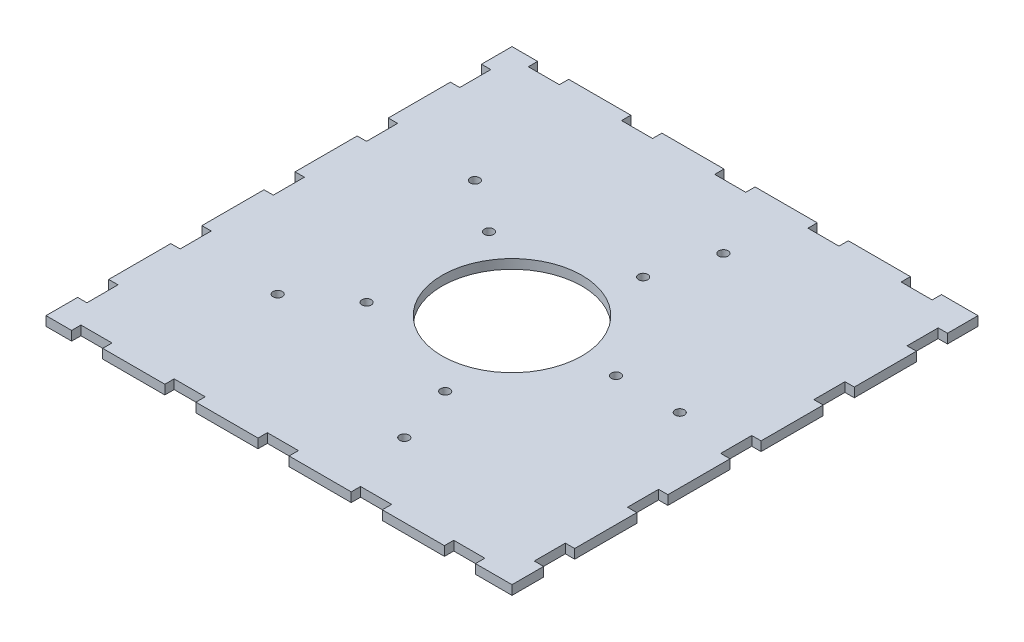
SolidWorks part; units mm, degrees
ref_plane "Front Plane" through (0, 0, 0) normal (0, 0, 1) x (1, 0, 0)
ref_plane "Top Plane" through (0, 0, 0) normal (0, 1, 0) x (1, 0, 0)
ref_plane "Right Plane" through (0, 0, 0) normal (1, 0, 0) x (0, 0, -1)
sketch "Sketch1" plane through (0, 0, 0) normal (0, 1, 0) x (-1, 0, 0)
  line L0 (75, -75) -> (-75, -75)
  line L1 (-75, -75) -> (-75, 75)
  line L2 (-75, 75) -> (75, 75)
  line L3 (75, 75) -> (75, -75)
  dimension "D1" = 150
  dimension "D2" = 150
extrude "Boss-Extrude1" add sketch "Sketch1" along normal blind 3 contours L0 L1 L2 L3
sketch "Sketch2" plane through (0, 3, 0) normal (0, 1, 0) x (1, 0, 0)
  circle A0 centre (0, 0) radius 22.5
  dimension "D1" = 45
extrude "Cut-Extrude1" cut sketch "Sketch2" against normal blind 3
sketch "Sketch3" plane through (0, 3, 0) normal (0, 1, 0) x (1, 0, 0)
  line L0 (-66.75, 75) -> (-66.75, 72)
  line L1 (-75, 75) -> (75, 75) construction
  line L2 (-66.75, 72) -> (-56.75, 72)
  line L3 (-56.75, 72) -> (-56.75, 75)
  line L4 (-56.75, 75) -> (-66.75, 75)
  line L5 (-75, 0) -> (75, 0) construction
  line L6 (-75, -75) -> (-75, 75) construction
  line L7 (75, 75) -> (75, -75) construction
  line L8 (-56.75, -75) -> (-66.75, -75)
  line L9 (-56.75, -72) -> (-56.75, -75)
  line L10 (-66.75, -72) -> (-56.75, -72)
  line L11 (-66.75, -75) -> (-66.75, -72)
  dimension "D1" = 10
  dimension "D2" = 3
extrude "Cut-Extrude2" cut sketch "Sketch3" against normal blind 3
pattern_linear "LPattern1" count 5 spacing 30 along (1, 0, 0) of "Cut-Extrude2"
sketch "Sketch4" plane through (0, 3, 0) normal (0, 1, 0) x (1, 0, 0)
  line L0 (-75, -64.8253) -> (-72, -64.8253)
  line L1 (-75, -75) -> (-75, 75) construction
  line L2 (-72, -64.8253) -> (-72, -54.8253)
  line L3 (-72, -54.8253) -> (-75, -54.8253)
  line L4 (-75, -54.8253) -> (-75, -64.8253)
  line L5 (0, 72) -> (0, -72) construction
  line L6 (-6.75, 72) -> (3.25, 72) construction
  line L7 (3.25, -72) -> (-6.75, -72) construction
  line L8 (75, -54.8253) -> (75, -64.8253)
  line L9 (72, -54.8253) -> (75, -54.8253)
  line L10 (72, -64.8253) -> (72, -54.8253)
  line L11 (75, -64.8253) -> (72, -64.8253)
  dimension "D1" = 10
  dimension "D2" = 3
extrude "Cut-Extrude3" cut sketch "Sketch4" against normal blind 3
pattern_linear "LPattern2" count 5 spacing 30 along (0, 0, -1) of "Cut-Extrude3"
sketch "Sketch5" plane through (0, 0, 0) normal (0, -1, 0) x (-1, 0, 0)
  circle A12 centre (0, 0) radius 54
  circle A13 centre (0, 0) radius 33.5
  circle A14 centre (-33.5, 0) radius 1.5
  circle A15 centre (-10.3521, 31.8604) radius 1.5
  circle A16 centre (27.1021, 19.6908) radius 1.5
  circle A17 centre (27.1021, -19.6908) radius 1.5
  circle A18 centre (-10.3521, -31.8604) radius 1.5
  circle A19 centre (-54, 0) radius 1.5
  circle A20 centre (-16.6869, 51.3571) radius 1.5
  circle A21 centre (43.6869, 31.7404) radius 1.5
  circle A22 centre (43.6869, -31.7404) radius 1.5
  circle A23 centre (-16.6869, -51.3571) radius 1.5
  point P15 (0, 0)
  point P18 (0, 0)
  point P27 (0, 0)
  point P28 (0, 0)
  dimension "D1" = 3
  dimension "D2" = 5
  dimension "D3" = 5
extrude "Cut-Extrude4" cut sketch "Sketch5" against normal blind 10 contours A17 | A18 | A14 | A15 | A16 | A21 | A22 | A23 | A19 | A20
